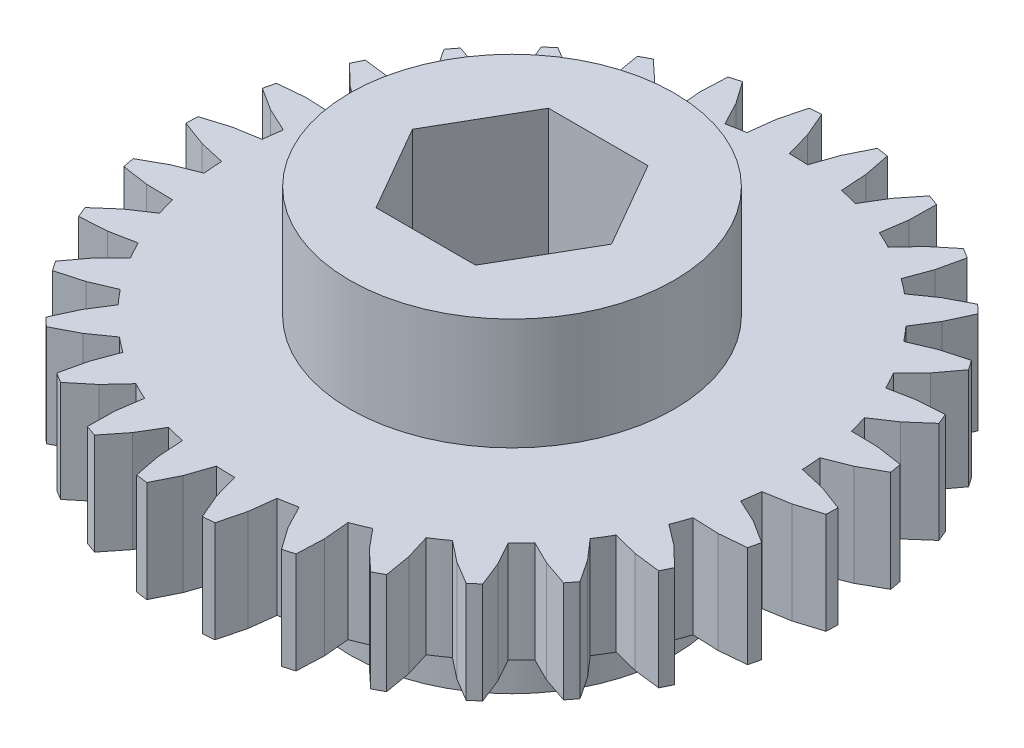
SolidWorks part; units mm, degrees
ref_plane "Front Plane" through (0, 0, 0) normal (0, 0, 1) x (1, 0, 0)
ref_plane "Top Plane" through (0, 0, 0) normal (0, 1, 0) x (1, 0, 0)
ref_plane "Right Plane" through (0, 0, 0) normal (1, 0, 0) x (0, 0, -1)
sketch "Sketch2" plane through (0, 0, 0) normal (0, 1, 0) x (1, 0, 0)
  circle A0 centre (0, 0) radius 15 construction
  circle A1 centre (0, 0) radius 16.25
  circle A2 centre (0, 0) radius 13.75 construction
  dimension "D1" = 30
  dimension "D2" = 1.25
  dimension "D3" = 1.25
extrude "Boss-Extrude1" add sketch "Sketch2" along normal blind 2.5 and the other way blind 2.5
sketch "Sketch1" plane through (0, 0, 0) normal (0, 1, 0) x (1, 0, 0)
  line L1 (1.2745, 14.9458) -> (0.8551, 13.7234)
  line L2 (0, 0) -> (-1419.6345, 49979.8423) construction
  line L3 (-0.4259, 14.994) -> (-0.0764, 13.7498)
  line L4 (-0.4259, 14.994) -> (-0.951, 16.2221)
  line L5 (0, 0) -> (1416.639, 49979.9273) construction
  line L6 (1.2745, 14.9458) -> (1.8683, 16.1422)
  line L7 (4.3541, 14.3542) -> (5.1836, 15.401)
  line L8 (4.3541, 14.3542) -> (3.6897, 13.2457)
  line L9 (2.7008, 14.7548) -> (2.784, 13.4652)
  line L10 (2.7008, 14.7548) -> (2.4426, 16.0654)
  line L11 (7.2433, 13.1352) -> (8.2724, 13.9868)
  line L12 (7.2433, 13.1352) -> (6.363, 12.1891)
  line L13 (5.7095, 13.8709) -> (5.5227, 12.5921)
  line L14 (5.7095, 13.8709) -> (5.7294, 15.2065)
  line L15 (9.816, 11.3422) -> (10.9997, 11.9612)
  line L16 (9.816, 11.3422) -> (8.7582, 10.5998)
  line L17 (8.4687, 12.3807) -> (8.0201, 11.1687)
  line L18 (8.4687, 12.3807) -> (8.7658, 13.683)
  line L19 (11.9597, 9.0535) -> (13.2462, 9.4128)
  line L20 (11.9597, 9.0535) -> (10.7707, 8.5473)
  line L21 (10.8577, 10.3494) -> (10.1669, 9.2572)
  line L22 (10.8577, 10.3494) -> (11.4191, 11.5614)
  line L23 (13.5807, 6.3691) -> (14.9137, 6.4531)
  line L24 (13.5807, 6.3691) -> (12.3124, 6.1211)
  line L25 (12.7722, 7.8658) -> (11.8695, 6.9411)
  line L26 (12.7722, 7.8658) -> (13.5733, 8.9346)
  line L27 (14.6081, 3.4064) -> (15.9295, 3.2114)
  line L28 (14.6081, 3.4064) -> (13.316, 3.4275)
  line L29 (14.1285, 5.0384) -> (13.0532, 4.3216)
  line L30 (14.1285, 5.0384) -> (15.1343, 5.9173)
  line L31 (14.9971, 0.2947) -> (16.2491, -0.1708)
  line L32 (14.9971, 0.2947) -> (13.7376, 0.584)
  line L33 (14.8673, 1.9909) -> (13.6665, 1.5132)
  line L34 (14.8673, 1.9909) -> (16.0339, 2.6414)
  line L35 (14.7307, -2.8298) -> (15.8585, -3.5454)
  line L36 (14.7307, -2.8298) -> (13.5588, -2.2849)
  line L37 (14.9563, -1.1437) -> (13.6825, -1.3612)
  line L38 (14.9563, -1.1437) -> (16.2327, -0.7499)
  line L39 (13.8204, -5.8306) -> (14.7748, -6.7651)
  line L40 (13.8204, -5.8306) -> (12.7875, -5.054)
  line L41 (14.3917, -4.2283) -> (13.1004, -4.1762)
  line L42 (14.3917, -4.2283) -> (15.722, -4.1085)
  line L43 (12.3062, -8.5766) -> (13.0454, -9.6891)
  line L44 (12.3062, -8.5766) -> (11.4572, -7.6023)
  line L45 (13.1981, -7.1281) -> (11.9459, -6.8087)
  line L46 (13.1981, -7.1281) -> (14.5243, -7.2875)
  line L47 (10.2541, -10.9478) -> (10.7459, -12.1897)
  line L48 (10.2541, -10.9478) -> (9.6263, -9.8182)
  line L49 (11.4277, -9.7164) -> (10.2692, -9.1436)
  line L50 (11.4277, -9.7164) -> (12.6917, -10.148)
  line L51 (7.7538, -12.8405) -> (7.9767, -14.1575)
  line L52 (7.7538, -12.8405) -> (7.3746, -11.6051)
  line L53 (9.1578, -11.88) -> (8.1438, -11.0789)
  line L54 (9.1578, -11.88) -> (10.3045, -12.565)
  line L55 (4.9147, -14.172) -> (4.8588, -15.5066)
  line L56 (4.9147, -14.172) -> (4.8006, -12.8847)
  line L57 (6.4877, -13.5244) -> (5.6624, -12.53)
  line L58 (6.4877, -13.5244) -> (7.4669, -14.4329)
  line L59 (1.8607, -14.8841) -> (1.5287, -16.1779)
  line L60 (1.8607, -14.8841) -> (2.0168, -13.6013)
  line L61 (3.534, -14.5778) -> (2.9335, -13.4334)
  line L62 (3.534, -14.5778) -> (4.303, -15.6699)
  line L63 (-1.2745, -14.9458) -> (-1.8683, -16.1422)
  line L64 (-1.2745, -14.9458) -> (-0.8551, -13.7234)
  line L65 (0.4259, -14.994) -> (0.0764, -13.7498)
  line L66 (0.4259, -14.994) -> (0.951, -16.2221)
  line L67 (-4.3541, -14.3542) -> (-5.1836, -15.401)
  line L68 (-4.3541, -14.3542) -> (-3.6897, -13.2457)
  line L69 (-2.7008, -14.7548) -> (-2.784, -13.4652)
  line L70 (-2.7008, -14.7548) -> (-2.4426, -16.0654)
  line L71 (-7.2433, -13.1352) -> (-8.2724, -13.9868)
  line L72 (-7.2433, -13.1352) -> (-6.363, -12.1891)
  line L73 (-5.7095, -13.8709) -> (-5.5227, -12.5921)
  line L74 (-5.7095, -13.8709) -> (-5.7294, -15.2065)
  line L75 (-9.816, -11.3422) -> (-10.9997, -11.9612)
  line L76 (-9.816, -11.3422) -> (-8.7582, -10.5998)
  line L77 (-8.4687, -12.3807) -> (-8.0201, -11.1687)
  line L78 (-8.4687, -12.3807) -> (-8.7658, -13.683)
  line L79 (-11.9597, -9.0535) -> (-13.2462, -9.4128)
  line L80 (-11.9597, -9.0535) -> (-10.7707, -8.5473)
  line L81 (-10.8577, -10.3494) -> (-10.1669, -9.2572)
  line L82 (-10.8577, -10.3494) -> (-11.4191, -11.5614)
  line L83 (-13.5807, -6.3691) -> (-14.9137, -6.4531)
  line L84 (-13.5807, -6.3691) -> (-12.3124, -6.1211)
  line L85 (-12.7722, -7.8658) -> (-11.8695, -6.9411)
  line L86 (-12.7722, -7.8658) -> (-13.5733, -8.9346)
  line L87 (-14.6081, -3.4064) -> (-15.9295, -3.2114)
  line L88 (-14.6081, -3.4064) -> (-13.316, -3.4275)
  line L89 (-14.1285, -5.0384) -> (-13.0532, -4.3216)
  line L90 (-14.1285, -5.0384) -> (-15.1343, -5.9173)
  line L91 (-14.9971, -0.2947) -> (-16.2491, 0.1708)
  line L92 (-14.9971, -0.2947) -> (-13.7376, -0.584)
  line L93 (-14.8673, -1.9909) -> (-13.6665, -1.5132)
  line L94 (-14.8673, -1.9909) -> (-16.0339, -2.6414)
  line L95 (-14.7307, 2.8298) -> (-15.8585, 3.5454)
  line L96 (-14.7307, 2.8298) -> (-13.5588, 2.2849)
  line L97 (-14.9563, 1.1437) -> (-13.6825, 1.3612)
  line L98 (-14.9563, 1.1437) -> (-16.2327, 0.7499)
  line L99 (-13.8204, 5.8306) -> (-14.7748, 6.7651)
  line L100 (-13.8204, 5.8306) -> (-12.7875, 5.054)
  line L101 (-14.3917, 4.2283) -> (-13.1004, 4.1762)
  line L102 (-14.3917, 4.2283) -> (-15.722, 4.1085)
  line L103 (-12.3062, 8.5766) -> (-13.0454, 9.6891)
  line L104 (-12.3062, 8.5766) -> (-11.4572, 7.6023)
  line L105 (-13.1981, 7.1281) -> (-11.9459, 6.8087)
  line L106 (-13.1981, 7.1281) -> (-14.5243, 7.2875)
  line L107 (-10.2541, 10.9478) -> (-10.7459, 12.1897)
  line L108 (-10.2541, 10.9478) -> (-9.6263, 9.8182)
  line L109 (-11.4277, 9.7164) -> (-10.2692, 9.1436)
  line L110 (-11.4277, 9.7164) -> (-12.6917, 10.148)
  line L111 (-7.7538, 12.8405) -> (-7.9767, 14.1575)
  line L112 (-7.7538, 12.8405) -> (-7.3746, 11.6051)
  line L113 (-9.1578, 11.88) -> (-8.1438, 11.0789)
  line L114 (-9.1578, 11.88) -> (-10.3045, 12.565)
  line L115 (-4.9147, 14.172) -> (-4.8588, 15.5066)
  line L116 (-4.9147, 14.172) -> (-4.8006, 12.8847)
  line L117 (-6.4877, 13.5244) -> (-5.6624, 12.53)
  line L118 (-6.4877, 13.5244) -> (-7.4669, 14.4329)
  line L119 (-1.8607, 14.8841) -> (-1.5287, 16.1779)
  line L120 (-1.8607, 14.8841) -> (-2.0168, 13.6013)
  line L121 (-3.534, 14.5778) -> (-2.9335, 13.4334)
  line L122 (-3.534, 14.5778) -> (-4.303, 15.6699)
  circle A0 centre (0, 0) radius 15 construction
  arc A1 (1.8683, 16.1422) -> (-0.951, 16.2221) centre (0, 0) ccw
  arc A2 (0.8551, 13.7234) -> (-0.0764, 13.7498) centre (0, 0) ccw
  circle A3 centre (0, 0) radius 13.75 construction
  arc A4 (5.1836, 15.401) -> (2.4426, 16.0654) centre (0, 0) ccw
  circle A5 centre (0, 0) radius 16.25 construction
  arc A6 (3.6897, 13.2457) -> (2.784, 13.4652) centre (0, 0) ccw
  arc A7 (8.2724, 13.9868) -> (5.7294, 15.2065) centre (0, 0) ccw
  arc A8 (6.363, 12.1891) -> (5.5227, 12.5921) centre (0, 0) ccw
  arc A9 (10.9997, 11.9612) -> (8.7658, 13.683) centre (0, 0) ccw
  arc A10 (8.7582, 10.5998) -> (8.0201, 11.1687) centre (0, 0) ccw
  arc A11 (13.2462, 9.4128) -> (11.4191, 11.5614) centre (0, 0) ccw
  arc A12 (10.7707, 8.5473) -> (10.1669, 9.2572) centre (0, 0) ccw
  arc A13 (14.9137, 6.4531) -> (13.5733, 8.9346) centre (0, 0) ccw
  arc A14 (12.3124, 6.1211) -> (11.8695, 6.9411) centre (0, 0) ccw
  arc A15 (15.9295, 3.2114) -> (15.1343, 5.9173) centre (0, 0) ccw
  arc A16 (13.316, 3.4275) -> (13.0532, 4.3216) centre (0, 0) ccw
  arc A17 (16.2491, -0.1708) -> (16.0339, 2.6414) centre (0, 0) ccw
  arc A18 (13.7376, 0.584) -> (13.6665, 1.5132) centre (0, 0) ccw
  arc A19 (15.8585, -3.5454) -> (16.2327, -0.7499) centre (0, 0) ccw
  arc A20 (13.5588, -2.2849) -> (13.6825, -1.3612) centre (0, 0) ccw
  arc A21 (14.7748, -6.7651) -> (15.722, -4.1085) centre (0, 0) ccw
  arc A22 (12.7875, -5.054) -> (13.1004, -4.1762) centre (0, 0) ccw
  arc A23 (13.0454, -9.6891) -> (14.5243, -7.2875) centre (0, 0) ccw
  arc A24 (11.4572, -7.6023) -> (11.9459, -6.8087) centre (0, 0) ccw
  arc A25 (10.7459, -12.1897) -> (12.6917, -10.148) centre (0, 0) ccw
  arc A26 (9.6263, -9.8182) -> (10.2692, -9.1436) centre (0, 0) ccw
  arc A27 (7.9767, -14.1575) -> (10.3045, -12.565) centre (0, 0) ccw
  arc A28 (7.3746, -11.6051) -> (8.1438, -11.0789) centre (0, 0) ccw
  arc A29 (4.8588, -15.5066) -> (7.4669, -14.4329) centre (0, 0) ccw
  arc A30 (4.8006, -12.8847) -> (5.6624, -12.53) centre (0, 0) ccw
  arc A31 (1.5287, -16.1779) -> (4.303, -15.6699) centre (0, 0) ccw
  arc A32 (2.0168, -13.6013) -> (2.9335, -13.4334) centre (0, 0) ccw
  arc A33 (-1.8683, -16.1422) -> (0.951, -16.2221) centre (0, 0) ccw
  arc A34 (-0.8551, -13.7234) -> (0.0764, -13.7498) centre (0, 0) ccw
  arc A35 (-5.1836, -15.401) -> (-2.4426, -16.0654) centre (0, 0) ccw
  arc A36 (-3.6897, -13.2457) -> (-2.784, -13.4652) centre (0, 0) ccw
  arc A37 (-8.2724, -13.9868) -> (-5.7294, -15.2065) centre (0, 0) ccw
  arc A38 (-6.363, -12.1891) -> (-5.5227, -12.5921) centre (0, 0) ccw
  arc A39 (-10.9997, -11.9612) -> (-8.7658, -13.683) centre (0, 0) ccw
  arc A40 (-8.7582, -10.5998) -> (-8.0201, -11.1687) centre (0, 0) ccw
  arc A41 (-13.2462, -9.4128) -> (-11.4191, -11.5614) centre (0, 0) ccw
  arc A42 (-10.7707, -8.5473) -> (-10.1669, -9.2572) centre (0, 0) ccw
  arc A43 (-14.9137, -6.4531) -> (-13.5733, -8.9346) centre (0, 0) ccw
  arc A44 (-12.3124, -6.1211) -> (-11.8695, -6.9411) centre (0, 0) ccw
  arc A45 (-15.9295, -3.2114) -> (-15.1343, -5.9173) centre (0, 0) ccw
  arc A46 (-13.316, -3.4275) -> (-13.0532, -4.3216) centre (0, 0) ccw
  arc A47 (-16.2491, 0.1708) -> (-16.0339, -2.6414) centre (0, 0) ccw
  arc A48 (-13.7376, -0.584) -> (-13.6665, -1.5132) centre (0, 0) ccw
  arc A49 (-15.8585, 3.5454) -> (-16.2327, 0.7499) centre (0, 0) ccw
  arc A50 (-13.5588, 2.2849) -> (-13.6825, 1.3612) centre (0, 0) ccw
  arc A51 (-14.7748, 6.7651) -> (-15.722, 4.1085) centre (0, 0) ccw
  arc A52 (-12.7875, 5.054) -> (-13.1004, 4.1762) centre (0, 0) ccw
  arc A53 (-13.0454, 9.6891) -> (-14.5243, 7.2875) centre (0, 0) ccw
  arc A54 (-11.4572, 7.6023) -> (-11.9459, 6.8087) centre (0, 0) ccw
  arc A55 (-10.7459, 12.1897) -> (-12.6917, 10.148) centre (0, 0) ccw
  arc A56 (-9.6263, 9.8182) -> (-10.2692, 9.1436) centre (0, 0) ccw
  arc A57 (-7.9767, 14.1575) -> (-10.3045, 12.565) centre (0, 0) ccw
  arc A58 (-7.3746, 11.6051) -> (-8.1438, 11.0789) centre (0, 0) ccw
  arc A59 (-4.8588, 15.5066) -> (-7.4669, 14.4329) centre (0, 0) ccw
  arc A60 (-4.8006, 12.8847) -> (-5.6624, 12.53) centre (0, 0) ccw
  arc A63 (-1.5287, 16.1779) -> (-4.303, 15.6699) centre (0, 0) ccw
  arc A64 (-2.0168, 13.6013) -> (-2.9335, 13.4334) centre (0, 0) ccw
  point P4 (0.4604, 16.2435)
  point P11 (-0.0764, 13.7498)
  point P12 (-0.4259, 14.994)
  point P15 (-0.951, 16.2221)
  point P18 (0.3896, 13.7445)
  point P192 (0, 0)
  dimension "D1" = 30
  dimension "D3" = 30
  dimension "D2" = 1.25
  dimension "D4" = 1.25
  dimension "D6" = 0.314
  dimension "D7" = 0.49
  dimension "D8" = 0.466
extrude "Cut-Extrude1" cut sketch "Sketch1" along normal through all and the other way through all
sketch "Sketch3" plane through (0, 0, 0) normal (0, 1, 0) x (1, 0, 0)
  circle A0 centre (0, 0) radius 8
  dimension "D1" = 16
extrude "Boss-Extrude2" add sketch "Sketch3" along normal blind 8 and the other way blind 8
sketch "Sketch4" plane through (0, 0, 0) normal (0, 1, 0) x (1, 0, 0)
  line L1 (4.9075, 0) -> (2.4537, 4.25)
  line L2 (2.4537, 4.25) -> (-2.4537, 4.25)
  line L3 (-2.4537, 4.25) -> (-4.9075, 0)
  line L4 (-4.9075, 0) -> (-2.4537, -4.25)
  line L5 (-2.4537, -4.25) -> (2.4537, -4.25)
  line L6 (2.4537, -4.25) -> (4.9075, 0)
  circle A0 centre (0, 0) radius 4.25 construction
  dimension "D1" = 8.5
extrude "Cut-Extrude2" cut sketch "Sketch4" against normal through all and the other way through all
